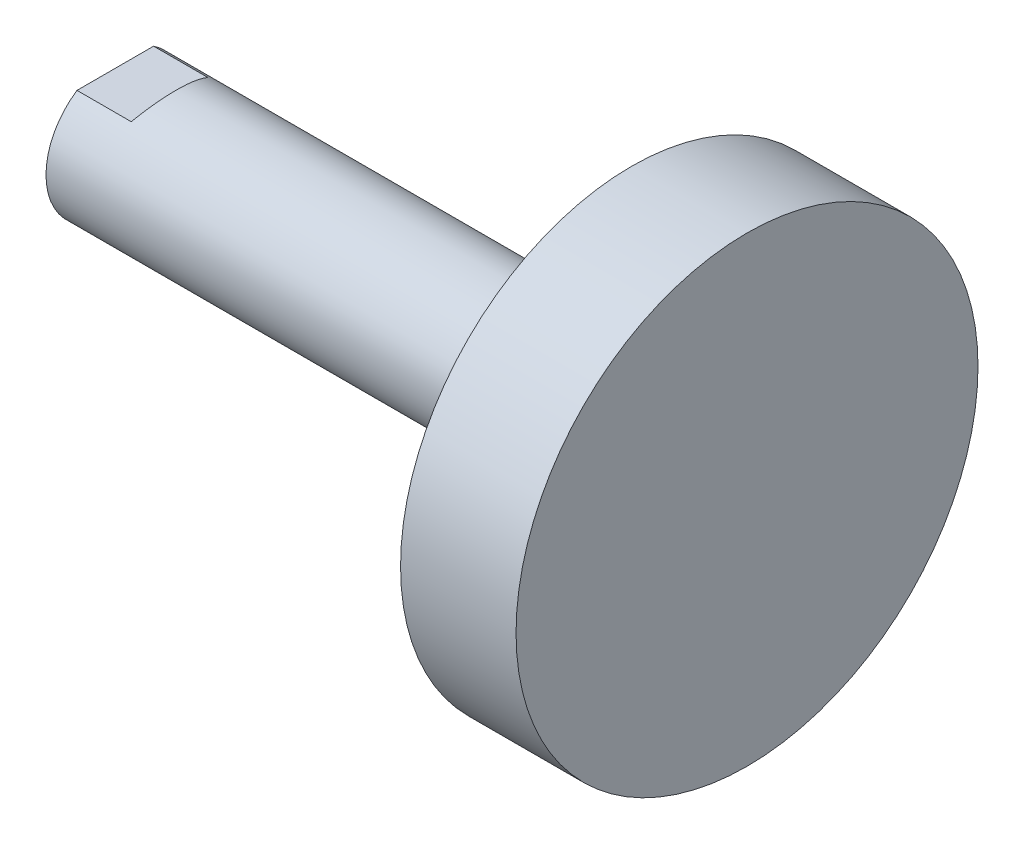
SolidWorks part; units mm, degrees
ref_plane "Ebene vorne" through (0, 0, 0) normal (0, 0, 1) x (1, 0, 0)
ref_plane "Ebene oben" through (0, 0, 0) normal (0, 1, 0) x (1, 0, 0)
ref_plane "Ebene rechts" through (0, 0, 0) normal (1, 0, 0) x (0, 0, -1)
sketch "Skizze1" plane through (0, 0, 0) normal (0, 0, 1) x (1, 0, 0)
  line L0 (-6.1, 0) -> (-6.1, 6)
  line L1 (-6.1, 6) -> (48.6, 6)
  line L2 (48.6, 6) -> (48.6, 0)
  line L3 (48.6, 0) -> (-6.1, 0)
  line L4 (48.6, 0) -> (-6.1, 0) construction
revolve "Rotation1" add sketch "Skizze1" angle 360 about L4 reverse direction yes
sketch "Skizze2" plane through (0, 0, 0) normal (0, 0, 1) x (1, 0, 0)
  line L0 (38.6, 0) -> (38.6, 20)
  line L1 (38.6, 20) -> (48.6, 20)
  line L2 (48.6, 20) -> (48.6, 0)
  line L3 (48.6, 0) -> (38.6, 0)
  line L4 (48.6, 0) -> (38.6, 0) construction
revolve "Rotation2" add sketch "Skizze2" angle 360 about L4 reverse direction yes
ref_plane "Ebene1" through (-6.1, 0, 0) normal (1, 0, 0) x (0, 0, -1)
sketch "Skizze3" plane through (0, 0, 0) normal (0, 0, 1) x (1, 0, 0)
  line L0 (-36.2, -16) -> (4.9509, -16)
  line L1 (4.9509, -16) -> (-1.4, -5)
  line L2 (-1.4, -5) -> (-6.1, -5)
  line L3 (-6.1, -5) -> (-6.1, -10)
  line L4 (-6.1, -10) -> (-30.1, -10)
  line L5 (-30.1, -10) -> (-30.1, 10)
  line L6 (-30.1, 10) -> (-6.1, 10)
  line L7 (-6.1, 10) -> (-6.1, 5)
  line L8 (-6.1, 5) -> (-1.4, 5)
  line L9 (-1.4, 5) -> (4.9509, 16)
  line L10 (4.9509, 16) -> (-36.2, 16)
  line L11 (-36.2, 16) -> (-36.2, -16)
extrude "Schnitt-Linear austragen1" cut sketch "Skizze3" along normal blind 12 and the other way blind 12
ref_plane "Ebene2" through (48.6, 0, 0) normal (1, 0, 0) x (0, 0, -1)
sketch "Skizze4" plane through (0, 0, 0) normal (0, 0, 1) x (1, 0, 0)
  line L0 (-6.1, 0) -> (-6.1, 4.8)
  line L1 (-6.1, 4.8) -> (-5.5, 4.2)
  line L2 (-5.5, 4.2) -> (-2.8, 4.2)
  line L3 (-2.8, 4.2) -> (-2.8, 4)
  line L4 (-2.8, 4) -> (-2.1235, 3.3235)
  line L5 (-2.1235, 3.3235) -> (13.9, 3.3235)
  line L6 (13.9, 3.3235) -> (15.8188, 0)
  line L7 (15.8188, 0) -> (-6.1, 0)
  line L8 (15.8188, 0) -> (-6.1, 0) construction
revolve "Schnitt-Rotation1" cut sketch "Skizze4" angle 360 about L8 reverse direction yes
cosmetic thread "Gewindedarstellung1" parameters "D1"=12.7, "D2"=8
ref_plane "Ebene3" through (-12.6, 0, 0) normal (1, 0, 0) x (0, 0, -1)
ref_plane "Ebene4" through (-6.1, 0, 0) normal (1, 0, 0) x (0, 0, -1)
ref_plane "Ebene5" through (0, 0, 0) normal (0, 0, 1) x (1, 0, 0)
ref_plane "FDT_PIRODACC_F1 XY" through (-6.1, 0, 0) normal (-1, 0, 0) x (0, 0, 1)
ref_plane "FDT_PIRODACC_F1 XZ" through (0, 0, 0) normal (0, 0, 1) x (1, 0, 0)
ref_plane "FDT_PIRODACC_F1 YZ" through (0, 0, 0) normal (0, 1, 0) x (1, 0, 0)
ref_axis "FDT_PIRODACC_F1 X" through (-6.1, -50, 0) along (0, 1, 0)
ref_axis "FDT_PIRODACC_F1 Y" through (-6.1, 0, 80.9) along (0, 0, -1)
ref_axis "FDT_PIRODACC_F1 Z" through (-80.9, 0, 0) along (1, 0, 0)
sketch3d "FDT_PIRODACC_F1"
  point P0 (-6.1, 0, 0)
ref_plane "NUT1 XY" through (-12.6, 0, 0) normal (1, 0, 0) x (0, 0, -1)
ref_plane "NUT1 XZ" through (0, 0, 0) normal (0, -1, 0) x (-1, 0, 0)
ref_plane "NUT1 YZ" through (0, 0, 0) normal (0, 0, -1) x (-1, 0, 0)
ref_axis "NUT1 X" through (-12.6, 0, 80.9) along (0, 0, -1)
ref_axis "NUT1 Y" through (-12.6, -50, 0) along (0, 1, 0)
ref_axis "NUT1 Z" through (80.9, 0, 0) along (-1, 0, 0)
sketch3d "NUT1"
  point P0 (-12.6, 0, 0)
ref_plane "PISTON XY" through (48.6, 0, 0) normal (1, 0, 0) x (0, 0, -1)
ref_plane "PISTON XZ" through (0, 0, 0) normal (0, -1, 0) x (-1, 0, 0)
ref_plane "PISTON YZ" through (0, 0, 0) normal (0, 0, -1) x (-1, 0, 0)
ref_axis "PISTON X" through (48.6, 0, 80.9) along (0, 0, -1)
ref_axis "PISTON Y" through (48.6, -50, 0) along (0, 1, 0)
ref_axis "PISTON Z" through (80.9, 0, 0) along (-1, 0, 0)
sketch3d "PISTON"
  point P0 (48.6, 0, 0)
